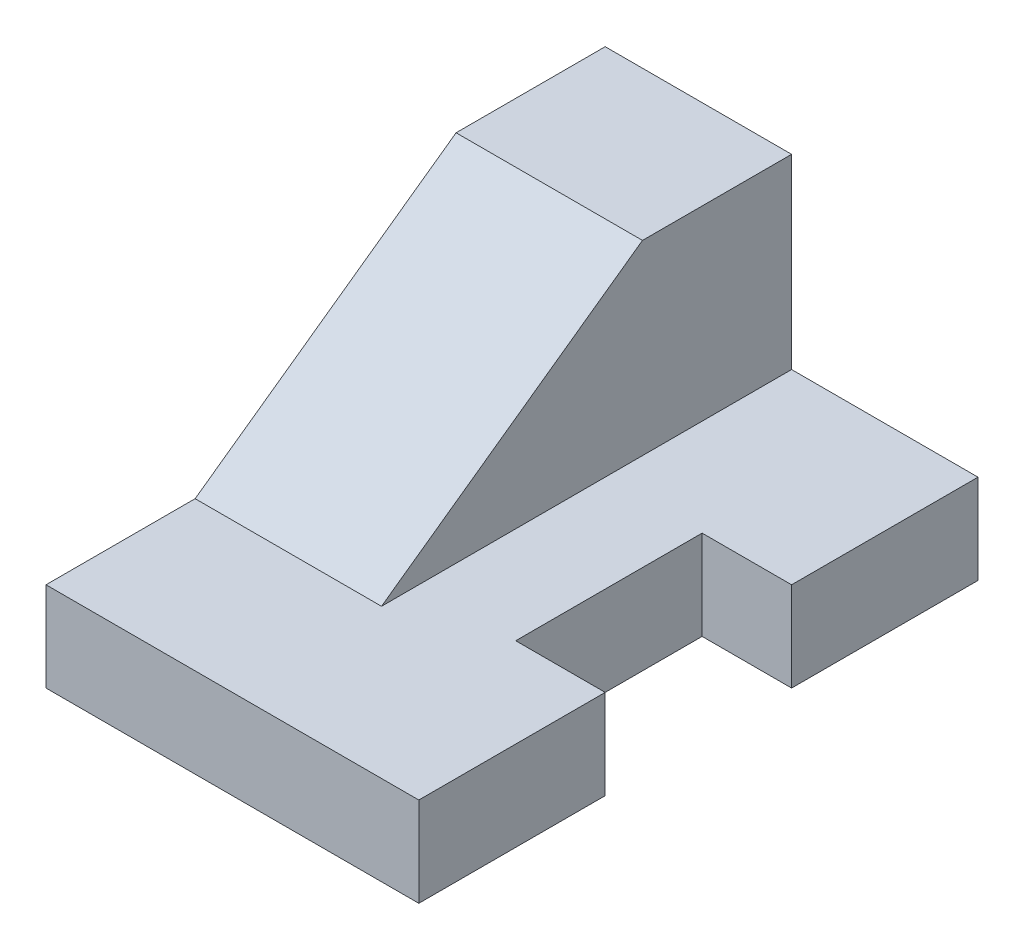
SolidWorks part; units mm, degrees
ref_plane "Front Plane" through (0, 0, 0) normal (0, 0, 1) x (1, 0, 0)
ref_plane "Top Plane" through (0, 0, 0) normal (0, 1, 0) x (1, 0, 0)
ref_plane "Right Plane" through (0, 0, 0) normal (1, 0, 0) x (0, 0, -1)
sketch "Sketch1" plane through (0, 0, 0) normal (1, 0, 0) x (0, 0, -1)
  line L0 (0, 0) -> (-75, 0)
  line L1 (-75, 0) -> (-75, 12)
  line L6 (-75, 12) -> (0, 12)
  line L7 (0, 12) -> (0, 0)
  line L8 (-55, 12) -> (-20, 37)
  line L9 (-20, 37) -> (0, 37)
  line L10 (0, 37) -> (0, 12)
  line L11 (-50, 12) -> (-50, 0)
  line L12 (-50, 0) -> (-25, 0)
  line L13 (-25, 0) -> (-25, 12)
  dimension "D1" = 75
  dimension "D2" = 25
  dimension "D3" = 25
  dimension "D4" = 25
  dimension "D5" = 20
  dimension "D6" = 20
  dimension "D7" = 12
extrude "Boss-Extrude2" add sketch "Sketch1" along normal blind 50 contours L11 L6 L1 L0 | L13 L0 L7 L6 region at (0, 6, 12.5) region at (0, 6, 62.5)
extrude "Boss-Extrude3" add sketch "Sketch1<4>" along normal blind 38 contours L0 L13 L6 L11 region at (0, 6, 37.5)
sketch "Sketch1<4>" plane through (0, 0, 0) normal (1, 0, 0) x (0, 0, -1) same geometry as "Sketch1"
extrude "Boss-Extrude4" add sketch "Sketch1<5>" along normal blind 25 contours L10 L9 L8 L6 region at (0, 22.5556, 20.1111)
sketch "Sketch1<5>" plane through (0, 0, 0) normal (1, 0, 0) x (0, 0, -1) same geometry as "Sketch1"
